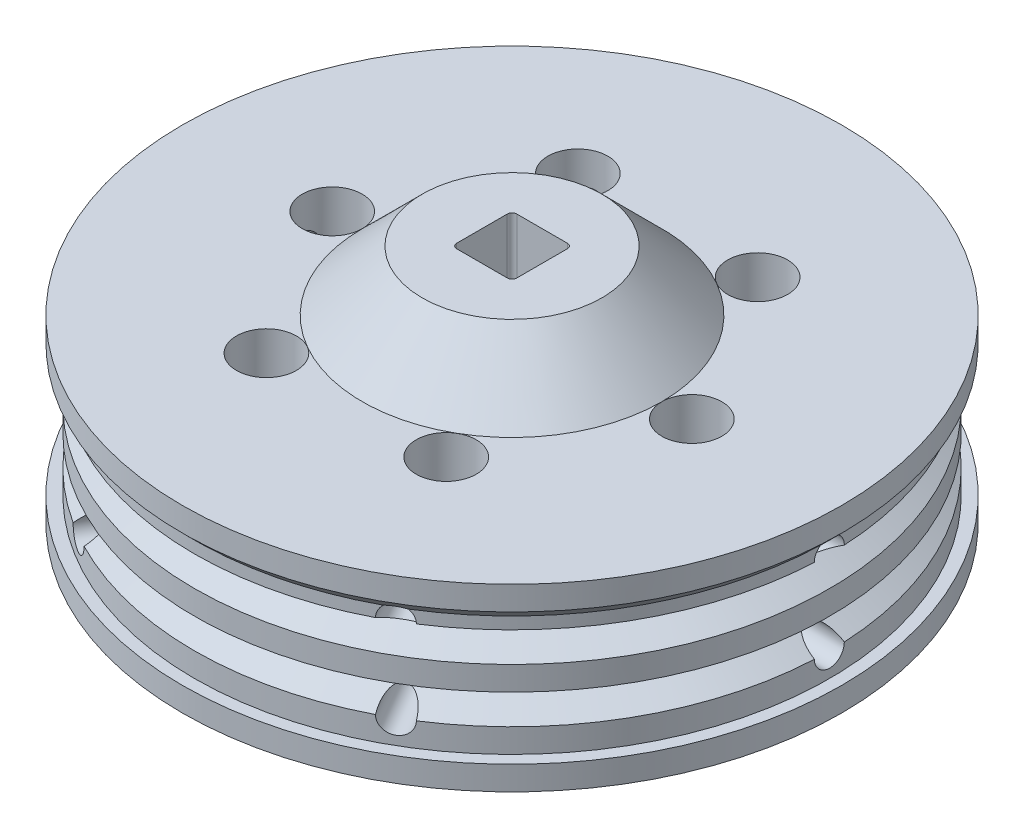
SolidWorks part; units mm, degrees
ref_plane "Front Plane" through (0, 0, 0) normal (0, 0, 1) x (1, 0, 0)
ref_plane "Top Plane" through (0, 0, 0) normal (0, 1, 0) x (1, 0, 0)
ref_plane "Right Plane" through (0, 0, 0) normal (1, 0, 0) x (0, 0, -1)
sketch "Sketch1" plane through (0, 0, 0) normal (0, 1, 0) x (1, 0, 0)
  circle A0 centre (0, 0) radius 17.4625
  dimension "D1" = 34.925
extrude "Boss-Extrude1" add sketch "Sketch1" along normal blind 9.525
sketch "Sketch2" plane through (0, 9.525, 0) normal (0, 1, 0) x (1, 0, 0)
  line L1 (-1.5938, 1.5938) -> (1.5939, 1.5938)
  line L2 (-1.5938, 1.5938) -> (-1.5938, -1.5939)
  line L3 (-1.5938, -1.5939) -> (1.5939, -1.5939)
  line L4 (1.5939, 1.5938) -> (1.5939, -1.5939)
  line L5 (-1.5938, 1.5938) -> (1.5939, -1.5939) construction
  line L6 (-1.5938, -1.5939) -> (1.5939, 1.5938) construction
  point P0 (0, 0)
  dimension "D1" = 3.1877
extrude "Cut-Extrude1" cut sketch "Sketch2" against normal through all
sketch "Sketch12" plane through (0, 9.525, 0) normal (0, 1, 0) x (1, 0, 0)
  line L0 (1.5939, 1.5938) -> (-1.5938, 1.5938)
  line L1 (-1.5938, 1.5938) -> (-1.5938, -1.5939)
  line L2 (-1.5938, -1.5939) -> (1.5939, -1.5939)
  line L3 (1.5939, -1.5939) -> (1.5939, 1.5938)
  line L4 (1.5939, -1.5939) -> (1.5939, 1.5938) construction
  line L5 (1.5939, 1.5938) -> (-1.5938, 1.5938) construction
  line L6 (-1.5938, -1.5939) -> (1.5939, -1.5939) construction
  line L7 (-1.5938, 1.5938) -> (-1.5938, -1.5939) construction
  circle A0 centre (0, 0) radius 4.7625
  dimension "D1" = 9.525
extrude "Boss-Extrude2" add sketch "Sketch12" along normal blind 3.175
sketch "Sketch3" plane through (0, 0, 0) normal (1, 0, 0) x (0, 0, -1)
  line L0 (-17.4625, 9.525) -> (-17.4625, 0) construction
  line L1 (-19.3675, 8.255) -> (-15.5575, 8.255)
  line L2 (-19.3675, 8.255) -> (-19.3675, 1.27)
  line L3 (-19.3675, 1.27) -> (-15.5575, 1.27)
  line L4 (-15.5575, 8.255) -> (-15.5575, 1.27)
  line L5 (-19.3675, 8.255) -> (-15.5575, 1.27) construction
  line L6 (-19.3675, 1.27) -> (-15.5575, 8.255) construction
  line L7 (17.4625, 9.525) -> (-17.4625, 9.525) construction
  point P0 (-17.4625, 4.7625)
  dimension "D1" = 1.27
  dimension "D2" = 3.81
revolve "Cut-Revolve1" cut sketch "Sketch3" angle 360 about axis through (0, 9.525, 0) along (0, -1, 0)
ref_plane "Plane1" through (0, 0, -15.5575) normal (0, 0, -1) x (-1, 0, 0)
sketch "Sketch5" plane through (0, 0, 0) normal (1, 0, 0) x (0, 0, -1)
  line L0 (15.5575, 8.255) -> (16.8275, 8.255)
  line L1 (15.5575, 1.27) -> (15.5575, 8.255) construction
  line L2 (16.8275, 8.255) -> (16.8275, 6.985)
  line L4 (15.5575, 6.985) -> (15.5575, 8.255)
  line L5 (15.5575, 1.27) -> (15.5575, 2.54)
  line L7 (16.8275, 2.54) -> (16.8275, 1.27)
  line L8 (16.8275, 1.27) -> (15.5575, 1.27)
  line L10 (16.8275, 5.3975) -> (16.8275, 4.1275)
  line L12 (15.5575, 4.1275) -> (15.5575, 5.3975)
  line L13 (17.4625, 1.27) -> (-17.4625, 1.27) construction
  line L14 (-17.4625, 8.255) -> (17.4625, 8.255) construction
  line L15 (16.8275, 4.1275) -> (15.5575, 3.3338)
  line L16 (15.5575, 3.3338) -> (16.8275, 2.54)
  line L17 (16.8275, 5.3975) -> (15.5575, 6.1913)
  line L18 (15.5575, 6.1913) -> (16.8275, 6.985)
  line L19 (15.5575, 4.1275) -> (15.5575, 3.3338)
  line L20 (15.5575, 5.3975) -> (15.5575, 6.1913)
  line L21 (15.5575, 2.54) -> (15.5575, 3.3338)
  line L22 (15.5575, 6.1913) -> (15.5575, 6.985)
  point P17 (15.5575, 4.7625)
  point P29 (15.5575, 4.7625)
  dimension "D1" = 1.27
  dimension "D2" = 1.27
revolve "Revolve1" add sketch "Sketch5" angle 360 about axis through (0, 9.525, 0) along (0, 1, 0) region at (0, 2.1192, -16.1421) region at (0, 4.7625, -16.1111) region at (0, 7.4058, -16.1421)
chamfer "Chamfer1" distance 0.635 angle 45 1 edges at (0, 8.255, 16.8275)
sketch "Sketch6" plane through (0, 9.525, 0) normal (0, 1, 0) x (1, 0, 0)
  line L0 (0, 0) -> (9.525, 0) construction
  circle A0 centre (9.525, 0) radius 1.5875
  dimension "D1" = 3.175
  dimension "D2" = 9.525
extrude "Cut-Extrude2" cut sketch "Sketch6" against normal through all
ref_plane "Plane2" through (16.8275, 0, 0) normal (1, 0, 0) x (0, 0, -1)
sketch "Sketch8" plane through (16.8275, 0, 0) normal (1, 0, 0) x (0, 0, -1)
  line L0 (0, 0) -> (0, 9.525)
  line L2 (1.5875, 9.525) -> (-1.5875, 9.525) construction
  line L3 (-17.4625, 0) -> (17.4625, 0) construction
  circle A1 centre (0, 6.985) radius 0.7937
  circle A2 centre (0, 2.54) radius 0.7938
  point P8 (0, 4.7625)
  dimension "D1" = 1.5875
  dimension "D3" = 2.54
  dimension "D2" = 2.54
extrude "Cut-Extrude3" cut sketch "Sketch8" against normal up to surface and the other way through all contours L0 | L0 | L0 A1 | L0 A1 | L0 A2 | L0 A2 region at (16.8275, 2.54, 0.3369) region at (16.8275, 6.985, 0.3369) region at (16.8275, 6.985, -0.3369) region at (16.8275, 2.54, -0.3369) up to face at (9.525, 0, 1.5875)
pattern_circular "CirPattern1" count 6 over 360 about axis through (0, 9.525, 0) along (0, 1, 0) of "Cut-Extrude2", "Cut-Extrude3"
chamfer "Chamfer2" distance 3.175 angle 45 1 edges at (0, 9.525, 4.7625)
fillet "Fillet3" radius 0.254 4 edges at (-1.5938, 6.35, 1.5939) (1.5939, 6.35, 1.5939) (1.5939, 6.35, -1.5938) (-1.5938, 6.35, -1.5938)
sketch "Sketch18" plane through (0, 0, 0) normal (1, 0, 0) x (0, 0, -1)
  line L0 (0, 0) -> (0, 9.525) construction
  line L1 (0, 7.3025) -> (15.7279, -1.778)
  line L2 (-17.4625, 0) -> (17.4625, 0) construction
  line L3 (17.4625, 9.525) -> (-17.4625, 9.525) construction
  line L4 (0, 7.3025) -> (15.7279, -1.778) construction
  line L5 (15.7279, -3.81) -> (15.7279, -1.778)
  line L6 (0, 5.5245) -> (15.7279, -3.81)
  line L7 (0, 5.5245) -> (0, 7.3025)
  line L8 (0, 7.3025) -> (15.7279, -1.778)
  point P12 (0, 4.7625)
  dimension "D1" = 60
  dimension "D2" = 2.032
  dimension "D3" = 1.778
  dimension "D4" = 1.778
  dimension "D5" = 2.54
revolve "Cut-Revolve2" cut sketch "Sketch18" angle 360 about L1 region at (0, 1.7074, -8.0387)
pattern_circular "CirPattern3" count 2 over 360 about axis through (0, 0, 0) along (0, 1, 0) of "Cut-Revolve2"
